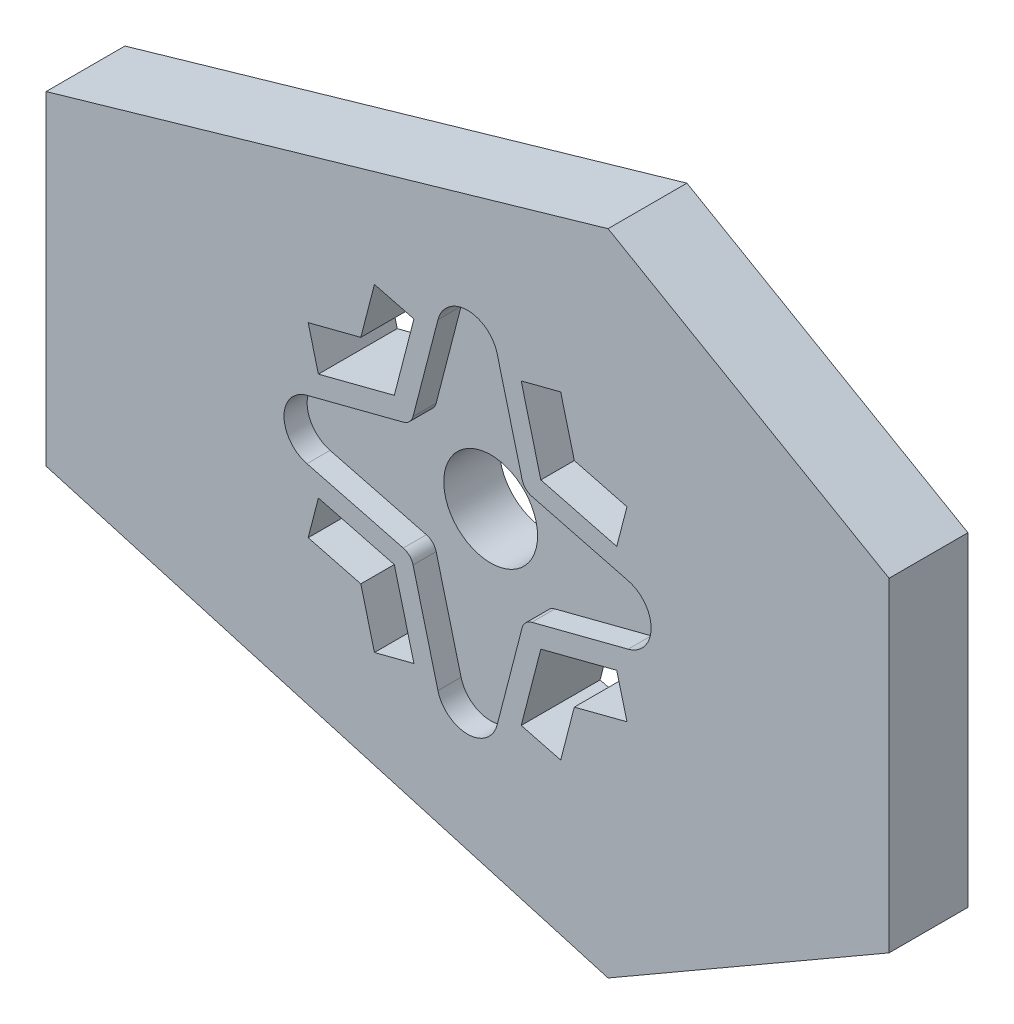
SolidWorks part; units mm, degrees
ref_plane "Front Plane" through (0, 0, 0) normal (0, 0, 1) x (1, 0, 0)
ref_plane "Top Plane" through (0, 0, 0) normal (0, 1, 0) x (1, 0, 0)
ref_plane "Right Plane" through (0, 0, 0) normal (1, 0, 0) x (0, 0, -1)
sketch "Sketch1" plane through (0, 0, 0) normal (0, 0, 1) x (1, 0, 0)
  line L0 (5.1833, -23.8638) -> (-36.15, -11.9319) construction
  line L1 (-36.15, 11.9319) -> (-36.15, -11.9319) construction
  line L2 (-36.15, 11.9319) -> (5.1833, 23.8638) construction
  line L3 (25.85, 11.9319) -> (5.1833, 23.8638) construction
  line L4 (25.85, -11.9319) -> (25.85, 11.9319) construction
  line L5 (5.1833, -23.8638) -> (25.85, -11.9319) construction
  line L6 (5.1833, -23.8638) -> (-36.15, -11.9319)
  line L7 (-36.15, 11.9319) -> (-36.15, -11.9319)
  line L8 (-36.15, 11.9319) -> (5.1833, 23.8638)
  line L9 (25.85, 11.9319) -> (5.1833, 23.8638)
  line L10 (25.85, -11.9319) -> (25.85, 11.9319)
  line L11 (5.1833, -23.8638) -> (25.85, -11.9319)
  line L20 (-2.9716, -11.813) -> (-1.1403, -4.7276)
  line L21 (-2.9716, -11.813) -> (-1.1403, -4.7276)
  line L22 (-0.4224, -4.0097) -> (6.663, -2.1784)
  line L23 (-0.4224, -4.0097) -> (6.663, -2.1784)
  line L24 (6.663, 2.1784) -> (-0.4224, 4.0097)
  line L25 (6.663, 2.1784) -> (-0.4224, 4.0097)
  line L26 (-1.1403, 4.7276) -> (-2.9716, 11.813)
  line L27 (-1.1403, 4.7276) -> (-2.9716, 11.813)
  line L28 (-7.3284, 11.813) -> (-9.1597, 4.7276)
  line L29 (-7.3284, 11.813) -> (-9.1597, 4.7276)
  line L30 (-9.8776, 4.0097) -> (-16.963, 2.1784)
  line L31 (-9.8776, 4.0097) -> (-16.963, 2.1784)
  line L32 (-16.963, -2.1784) -> (-9.8776, -4.0097)
  line L33 (-16.963, -2.1784) -> (-9.8776, -4.0097)
  line L34 (-9.1597, -4.7276) -> (-7.3284, -11.813)
  line L35 (-9.1597, -4.7276) -> (-7.3284, -11.813)
  circle A0 centre (-5.15, 0) radius 3.45 construction
  circle A1 centre (-5.15, 0) radius 3.45
  arc A9 (6.663, -2.1784) -> (6.663, 2.1784) centre (6.1, 0) ccw
  arc A11 (-2.9716, 11.813) -> (-7.3284, 11.813) centre (-5.15, 11.25) ccw
  arc A13 (-16.963, 2.1784) -> (-16.963, -2.1784) centre (-16.4, 0) ccw
  arc A15 (-7.3284, -11.813) -> (-2.9716, -11.813) centre (-5.15, -11.25) ccw
  arc A17 (6.663, -2.1784) -> (6.663, 2.1784) centre (6.1, 0) ccw
  arc A19 (-2.9716, 11.813) -> (-7.3284, 11.813) centre (-5.15, 11.25) ccw
  arc A21 (-16.963, 2.1784) -> (-16.963, -2.1784) centre (-16.4, 0) ccw
  arc A23 (-7.3284, -11.813) -> (-2.9716, -11.813) centre (-5.15, -11.25) ccw
  arc A30 (-0.4224, -4.0097) -> (-1.1403, -4.7276) centre (-0.1722, -4.9778) ccw
  arc A31 (-0.4224, -4.0097) -> (-1.1403, -4.7276) centre (-0.1722, -4.9778) ccw
  arc A32 (-1.1403, 4.7276) -> (-0.4224, 4.0097) centre (-0.1722, 4.9778) ccw
  arc A33 (-1.1403, 4.7276) -> (-0.4224, 4.0097) centre (-0.1722, 4.9778) ccw
  arc A34 (-9.8776, 4.0097) -> (-9.1597, 4.7276) centre (-10.1278, 4.9778) ccw
  arc A35 (-9.8776, 4.0097) -> (-9.1597, 4.7276) centre (-10.1278, 4.9778) ccw
  arc A36 (-9.1597, -4.7276) -> (-9.8776, -4.0097) centre (-10.1278, -4.9778) ccw
  arc A37 (-9.1597, -4.7276) -> (-9.8776, -4.0097) centre (-10.1278, -4.9778) ccw
  dimension "D1" = 0
extrude "Boss-Extrude1" add sketch "Sketch1" along normal up to surface (4.1 mm away) contours L8 L9 L10 L11 L6 L7 | A1
extrude "Boss-Extrude2" add sketch "Sketch1<3>" along normal up to surface (5.8 mm away) contours L6 L11 L10 L9 L8 L7 A23 A21 A19 A17 region at (-15.2663, -17.1461, 0)
sketch "Sketch1<3>" plane through (0, 0, 0) normal (0, 0, 1) x (1, 0, 0) same geometry as "Sketch1"
sketch "Sketch3" plane through (0, 0, 5.8) normal (0, 0, 1) x (1, 0, 0)
  line L0 (-13.0004, 7.8504) -> (-16.8732, 6.8495) construction
  line L1 (-16.8732, 6.8495) -> (-16.1225, 3.9449) construction
  line L2 (-10.5382, 5.3882) -> (-16.1225, 3.9449) construction
  line L3 (-9.0949, 10.9725) -> (-10.5382, 5.3882) construction
  line L4 (-11.9995, 11.7232) -> (-9.0949, 10.9725) construction
  line L5 (-11.9995, 11.7232) -> (-13.0004, 7.8504) construction
  line L6 (-13.0004, 7.8504) -> (-16.8732, 6.8495)
  line L7 (-16.8732, 6.8495) -> (-16.1225, 3.9449)
  line L8 (-10.5382, 5.3882) -> (-16.1225, 3.9449)
  line L9 (-9.0949, 10.9725) -> (-10.5382, 5.3882)
  line L10 (-11.9995, 11.7232) -> (-9.0949, 10.9725)
  line L11 (-11.9995, 11.7232) -> (-13.0004, 7.8504)
extrude "Cut-Extrude1" cut sketch "Sketch3" against normal through all
sketch "Sketch4" plane through (0, 0, 5.8) normal (0, 0, 1) x (1, 0, 0)
  line L0 (-5.15, 13.5) -> (-5.15, -13.5) construction
  line L1 (-18.65, 0) -> (8.35, 0) construction
  arc A0 (-2.9716, 11.813) -> (-7.3284, 11.813) centre (-5.15, 11.25) ccw construction
  arc A1 (-7.3284, -11.813) -> (-2.9716, -11.813) centre (-5.15, -11.25) ccw construction
  arc A2 (-16.963, 2.1784) -> (-16.963, -2.1784) centre (-16.4, 0) ccw construction
  arc A3 (6.663, -2.1784) -> (6.663, 2.1784) centre (6.1, 0) ccw construction
ref_plane "Plane1" through (-5.15, 0, 0) normal (-1, 0, 0) x (0, -1, 0)
ref_plane "Plane2" through (0, 0, 0) normal (0, -1, 0) x (1, 0, 0)
mirror "Mirror1" about plane through (-5.15, 0, 0) normal (-1, 0, 0) of "Cut-Extrude1"
mirror "Mirror2" about plane through (0, 0, 0) normal (0, -1, 0) of "Cut-Extrude1", "Mirror1"
